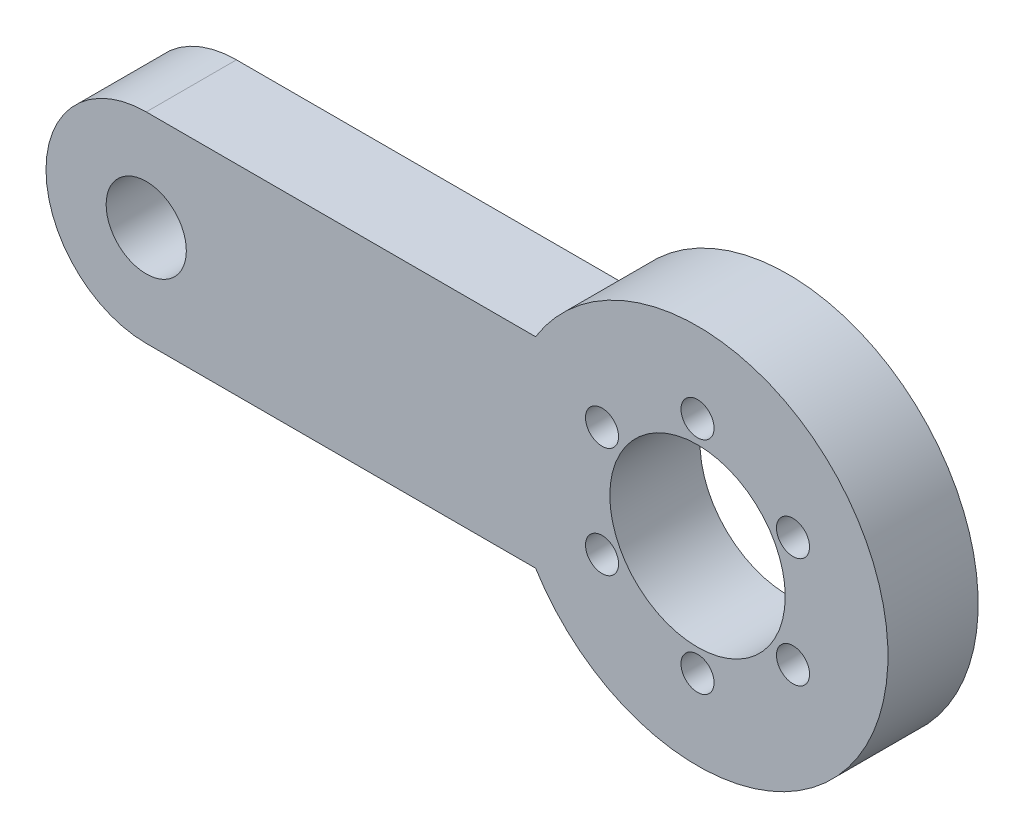
SolidWorks part; units mm, degrees
ref_plane "Plan de face" through (0, 0, 0) normal (0, 0, 1) x (1, 0, 0)
ref_plane "Plan de dessus" through (0, 0, 0) normal (0, 1, 0) x (1, 0, 0)
ref_plane "Plan de droite" through (0, 0, 0) normal (1, 0, 0) x (0, 0, -1)
sketch "Esquisse1" plane through (0, 0, 0) normal (0, 0, 1) x (1, 0, 0)
  line L1 (0, 0) -> (50, 0)
  line L2 (0, 0) -> (0, 20)
  line L3 (0, 20) -> (50, 20)
  line L4 (50, 0) -> (50, 20)
  dimension "D1" = 50
  dimension "D2" = 20
extrude "Boss.-Extru.1" add sketch "Esquisse1" along normal blind 9
sketch "Esquisse2" plane through (0, 0, 9) normal (0, 0, 1) x (1, 0, 0)
  line L0 (50, 25) -> (50, -5)
  line L1 (50, 0) -> (50, 20) construction
  line L2 (50, -5) -> (80, -5)
  line L3 (80, -5) -> (80, 25)
  line L4 (80, 10) -> (50, 10) construction
  line L5 (50, 25) -> (80, 25)
  dimension "D1" = 30
  dimension "D2" = 30
extrude "Boss.-Extru.2" add sketch "Esquisse2" against normal up to vertex (9 mm away) up to point (0, 20, 0)
sketch "Esquisse3" plane through (0, 0, 9) normal (0, 0, 1) x (1, 0, 0)
  line L0 (65, -5) -> (65, 25) construction
  line L1 (50, -5) -> (80, -5) construction
  line L2 (80, 25) -> (50, 25) construction
  circle A0 centre (65, 10) radius 8.75
  circle A1 centre (65, -1) radius 1.65
  circle A2 centre (55.4737, 4.5) radius 1.65
  circle A3 centre (55.4737, 15.5) radius 1.65
  circle A4 centre (65, 21) radius 1.65
  circle A5 centre (74.5263, 15.5) radius 1.65
  circle A6 centre (74.5263, 4.5) radius 1.65
  point P10 (60.9316, 7.1224)
  point P11 (75, 10)
  point P22 (65, 10)
  dimension "D1" = 17.5
  dimension "D2" = 11
  dimension "D3" = 3.3
  dimension "D4" = 6
extrude "Enlèv. mat.-Extru.1" cut sketch "Esquisse3" against normal through all both and the other way through all
sketch "Esquisse4" plane through (0, 0, 9) normal (0, 0, 1) x (1, 0, 0)
  line L0 (10, 20) -> (10, 0) construction
  line L1 (50, 20) -> (0, 20) construction
  line L2 (0, 0) -> (50, 0) construction
  line L3 (0, 20) -> (0, 0) construction
  circle A0 centre (10, 10) radius 4
  dimension "D1" = 8
  dimension "D2" = 10
extrude "Enlèv. mat.-Extru.2" cut sketch "Esquisse4" against normal through all both and the other way through all
fillet "Congé1" radius 10 2 edges at (0, 0, 4.5) (0, 20, 4.5)
sketch "Esquisse6" plane through (0, 0, 9) normal (0, 0, 1) x (1, 0, 0)
  circle A0 centre (65, 10) radius 14
  circle A1 centre (65, 10) radius 19
  dimension "D1" = 38
  dimension "D2" = 28
extrude "Boss.-Extru.3" add sketch "Esquisse6" against normal up to vertex (9 mm away) up to point (50, 25, 0)
sketch "Esquisse7" plane through (0, 0, 9) normal (0, 0, 1) x (1, 0, 0)
  line L0 (10, 0) -> (48.8445, 0) construction
  line L1 (48.8445, 0) -> (48.8445, -10.5)
  line L2 (48.8445, -10.5) -> (84.8445, -10.5)
  line L3 (84.8445, -10.5) -> (84.8445, 30.5)
  line L4 (84.8445, 10) -> (65, 10) construction
  line L5 (48.8445, 30.5) -> (84.8445, 30.5)
  line L6 (48.8445, 20) -> (48.8445, 30.5)
  circle A0 centre (65, 10) radius 19 construction
  arc A1 (48.8445, 20) -> (48.8445, 0) centre (65, 10) cw
  dimension "D1" = 38
  dimension "D2" = 36
  dimension "D3" = 41
extrude "Enlèv. mat.-Extru.4" cut sketch "Esquisse7" against normal through all
